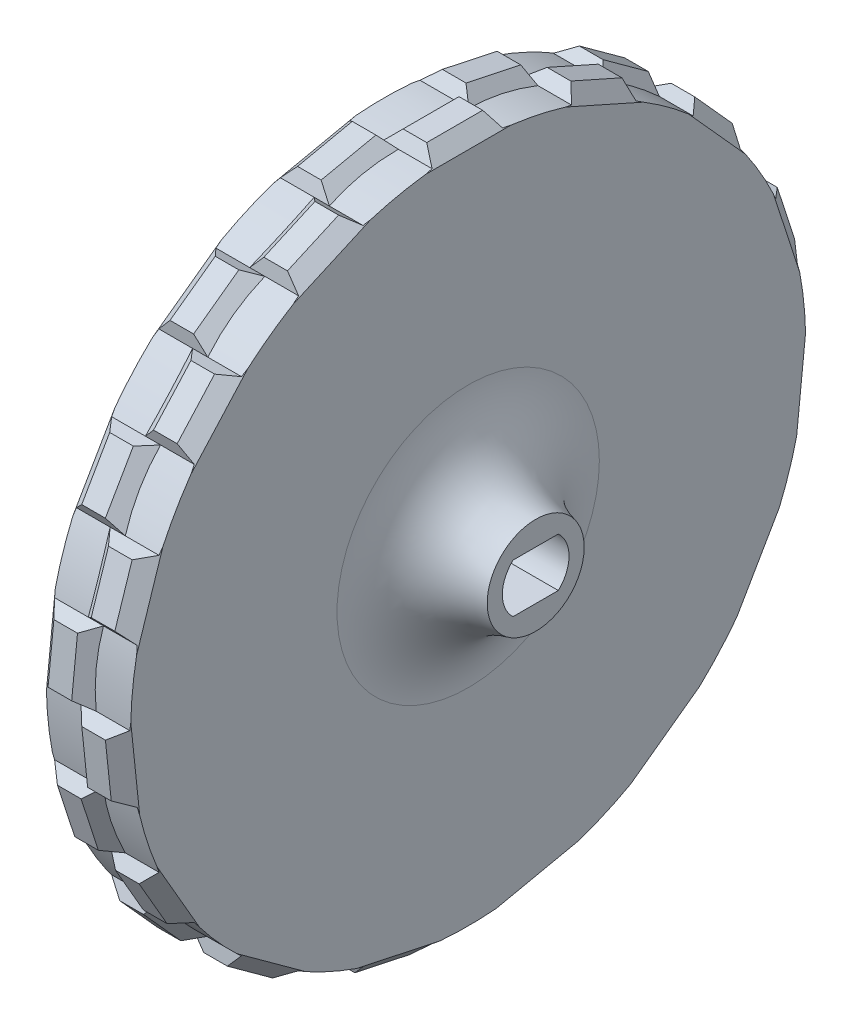
SolidWorks part; units mm, degrees
ref_plane "Front Plane" through (0, 0, 0) normal (0, 0, 1) x (1, 0, 0)
ref_plane "Top Plane" through (0, 0, 0) normal (0, 1, 0) x (1, 0, 0)
ref_plane "Right Plane" through (0, 0, 0) normal (1, 0, 0) x (0, 0, -1)
sketch "Sketch1" plane through (0, 0, 0) normal (1, 0, 0) x (0, 0, -1)
  circle A0 centre (0, 0) radius 40
  dimension "D1" = 80
extrude "Boss-Extrude1" add sketch "Sketch1" along normal blind 10
sketch "Sketch2" plane through (10, 0, 0) normal (1, 0, 0) x (0, 0, -1)
  line L0 (-4.1811, 39.7809) -> (-3.3151, 41.2809)
  line L1 (-3.3151, 41.2809) -> (3.3151, 41.2809)
  line L2 (3.3151, 41.2809) -> (4.1811, 39.7809)
  line L3 (4.1811, 39.7809) -> (-4.1811, 39.7809)
  line L4 (-4.1811, 39.7809) -> (0, 0) construction
  line L5 (0, 0) -> (4.1811, 39.7809) construction
  circle A0 centre (0, 0) radius 40 construction
  point P4 (0, 39.7809)
  dimension "D1" = 60
  dimension "D2" = 60
  dimension "D4" = 1.5
  dimension "D3" = 12
extrude "Boss-Extrude2" add sketch "Sketch2" against normal blind 6
chamfer "Chamfer1" distance 1.6 angle 45 2 edges at (10, 41.2809, 0) (4, 41.2809, 0)
pattern_circular "CirPattern1" count 15 over 360 about axis through (10, 0, 0) along (1, 0, 0) of "Boss-Extrude2", "Chamfer1"
sketch "Sketch4" plane through (0, 0, 0) normal (-1, 0, 0) x (0, 0, 1)
  line L0 (0, 40) -> (0, 0) construction
  line L1 (0, 0) -> (-8.3165, 39.1259) construction
  line L6 (-12.3607, 38.0423) -> (-4.1811, 39.7809)
  line L7 (-4.1811, 39.7809) -> (-5.3401, 41.068)
  line L8 (-5.3401, 41.068) -> (-11.8254, 39.6895)
  line L9 (-11.8254, 39.6895) -> (-12.3607, 38.0423)
  line L10 (-12.3607, 38.0423) -> (0, 0) construction
  line L11 (0, 0) -> (-4.1811, 39.7809) construction
  circle A1 centre (0, 0) radius 40 construction
  point P13 (-8.2709, 38.9116)
  dimension "D2" = 60
  dimension "D1" = 12
  dimension "D3" = 60
  dimension "D4" = 12
  dimension "D5" = 1.5
extrude "Boss-Extrude3" add sketch "Sketch4" against normal blind 6
chamfer "Chamfer2" distance 1.6 angle 45 2 edges at (6, 40.3788, -8.5828) (0, 40.3788, -8.5828)
pattern_circular "CirPattern2" count 15 over 360 about axis through (0, 0, 0) along (1, 0, 0) of "Boss-Extrude3", "Chamfer2"
sketch "Sketch5" plane through (10, 0, 0) normal (1, 0, 0) x (0, 0, -1)
  circle A0 centre (0, 0) radius 5.75
  dimension "D1" = 11.5
extrude "Boss-Extrude4" add sketch "Sketch5" along normal blind 8
sketch "Sketch6" plane through (18, 0, 0) normal (1, 0, 0) x (0, 0, -1)
  line L0 (-2.6819, 2.9) -> (2.6819, 2.9)
  line L1 (2.6819, -2.9) -> (-2.6819, -2.9)
  circle A0 centre (0, 0) radius 3.95
  dimension "D1" = 7.9
  dimension "D2" = 5.8
extrude "Cut-Extrude1" cut sketch "Sketch6" against normal blind 8.1 contours L0 A0 L1 region at (18, 0, 0)
fillet "Fillet1" radius 10 1 edges at (10, 0, -5.75)
equation "\"D2@Sketch2\"=\"D1@Sketch2\""
equation "\"D3@Sketch4\"=\"D2@Sketch4\""
equation "\"Num Treads\"= 15"
equation "\"D1@CirPattern1\"=\"Num Treads\""
equation "\"D1@CirPattern2\"=\"Num Treads\""
